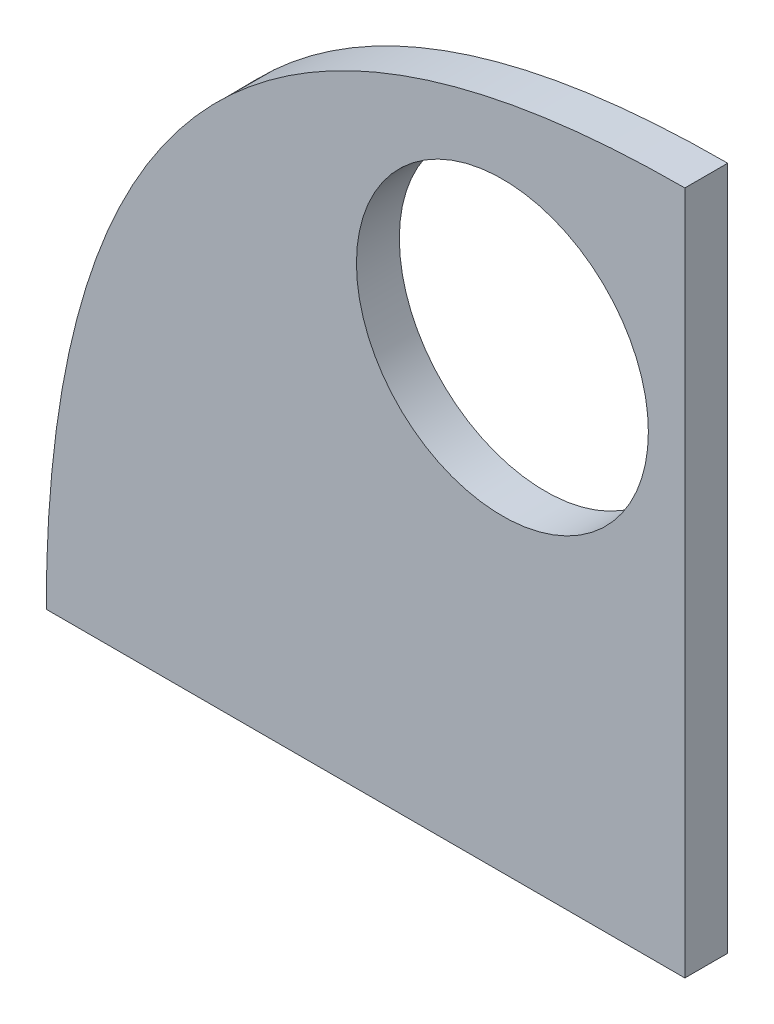
SolidWorks part; units mm, degrees
material "PLA"
ref_plane "Front Plane" through (0, 0, 0) normal (0, 0, 1) x (1, 0, 0)
ref_plane "Top Plane" through (0, 0, 0) normal (0, 1, 0) x (1, 0, 0)
ref_plane "Right Plane" through (0, 0, 0) normal (1, 0, 0) x (0, 0, -1)
sketch "Sketch1" plane through (0, 0, 0) normal (0, 0, 1) x (1, 0, 0)
  line L0 (0, 0) -> (0, 75)
  line L1 (0, 0) -> (-70, 0)
  line L2 (0, 75) -> (-70, 75) construction
  line L3 (-70, 75) -> (-70, 0) construction
  line L4 (-18.1972, 13) -> (-3.9, 13)
  line L5 (-36.1, 7) -> (-21.8028, 7)
  line L6 (-36.1, 7) -> (-36.1, 13)
  line L7 (-36.1, 13) -> (-21.8028, 13)
  line L8 (-3.9, 7) -> (-3.9, 13)
  line L9 (-36.1, 7) -> (-3.9, 13) construction
  line L10 (-36.1, 13) -> (-3.9, 7) construction
  line L11 (-18.1972, 7) -> (-3.9, 7)
  circle A1 centre (-20, 49.85) radius 16
  arc A2 (-18.1972, 13) -> (-21.8028, 13) centre (-20, 10) ccw
  arc A4 (-21.8028, 7) -> (-18.1972, 7) centre (-20, 10) ccw
  spline S0 degree 2 poles (0, 75) (-70, 75) (-70, 0) knots 0 0 0 1 1 1
  point P7 (-20, 10)
  point P10 (-20, 10)
  dimension "D1" = 70
  dimension "D2" = 32
  dimension "D8" = 32.2
  dimension "D10" = 7
  dimension "D3" = 75
  dimension "D4" = 10
  dimension "D5" = 20
  dimension "D6" = 39.85
  dimension "D7" = 70
  dimension "D9" = 6
extrude "Boss-Extrude1" add sketch "Sketch1" along normal blind 4.7 contours L5 L8 L7 L6 | L0 S0 L1 L8 L5 L6 L7 A1 region at (-33.9995, 30.3181, 0) region at (-20, 10, 0)
extrude "Cut-Extrude1" cut sketch "Sketch1<5>" along normal blind 1.7 contours L5 L8 L7 L6 region at (-20, 10, 0)
sketch "Sketch1<5>" plane through (0, 0, 0) normal (0, 0, 1) x (1, 0, 0) same geometry as "Sketch1"
